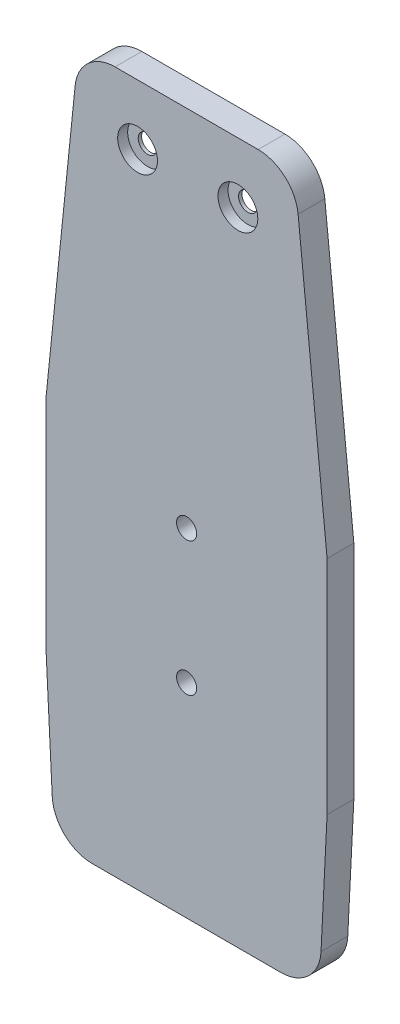
SolidWorks part; units mm, degrees
ref_plane "Front Plane" through (0, 0, 0) normal (0, 0, 1) x (1, 0, 0)
ref_plane "Top Plane" through (0, 0, 0) normal (0, 1, 0) x (1, 0, 0)
ref_plane "Right Plane" through (0, 0, 0) normal (1, 0, 0) x (0, 0, -1)
sketch "Sketch1" plane through (0, 0, 0) normal (0, 0, 1) x (1, 0, 0)
  line L8 (37.09, -18.2996) -> (38, -0.0999)
  line L9 (38, -0.0999) -> (38, 33.052)
  line L10 (33.663, 75.4585) -> (38, 33.052)
  line L11 (6.3059, 80.848) -> (27.6941, 80.848)
  line L12 (0.337, 75.4585) -> (-4, 33.052)
  line L13 (-4, -0.0999) -> (-4, 33.052)
  line L14 (-4, -0.0999) -> (-3.09, -18.2996)
  line L15 (2.9025, -24) -> (31.0975, -24)
  arc A4 (33.663, 75.4585) -> (27.6941, 80.848) centre (27.6941, 74.848) ccw
  arc A5 (0.337, 75.4585) -> (6.3059, 80.848) centre (6.3059, 74.848) cw
  arc A6 (-3.09, -18.2996) -> (2.9025, -24) centre (2.9025, -18) ccw
  arc A7 (31.0975, -24) -> (37.09, -18.2996) centre (31.0975, -18) ccw
extrude "Boss-Extrude4" add sketch "Sketch1" along normal blind 2
sketch "Sketch5" plane through (0, 0, 0) normal (0, 0, -1) x (-1, 0, 0)
  line L8 (-33.663, 75.4585) -> (-38, 33.052)
  line L9 (-38, 33.052) -> (-38, -0.0999)
  line L10 (-38, -0.0999) -> (-37.09, -18.2996)
  line L11 (-31.0975, -24) -> (-2.9025, -24)
  line L12 (3.09, -18.2996) -> (4, -0.0999)
  line L13 (4, -0.0999) -> (4, 33.052)
  line L14 (4, 33.052) -> (-0.337, 75.4585)
  line L15 (-6.3059, 80.848) -> (-27.6941, 80.848)
  line L16 (-31.0975, -22) -> (-2.9025, -22)
  line L17 (1.0925, -18.1998) -> (2, -0.05)
  line L18 (2, -0.05) -> (2, 32.95)
  line L19 (2, 32.95) -> (-2.3266, 75.255)
  line L20 (-6.3059, 78.848) -> (-27.6941, 78.848)
  line L21 (-31.6734, 75.255) -> (-36, 32.95)
  line L22 (-36, 32.95) -> (-36, -0.05)
  line L23 (-36, -0.05) -> (-35.0925, -18.1998)
  line L24 (-31.0975, -22) -> (-2.9025, -22)
  line L25 (1.0925, -18.1998) -> (2, -0.05)
  line L26 (2, -0.05) -> (2, 32.95)
  line L27 (2, 32.95) -> (-2.3266, 75.255)
  line L28 (-6.3059, 78.848) -> (-27.6941, 78.848)
  line L29 (-31.6734, 75.255) -> (-36, 32.95)
  line L30 (-36, 32.95) -> (-36, -0.05)
  line L31 (-36, -0.05) -> (-35.0925, -18.1998)
  arc A4 (-27.6941, 80.848) -> (-33.663, 75.4585) centre (-27.6941, 74.848) ccw
  arc A5 (-37.09, -18.2996) -> (-31.0975, -24) centre (-31.0975, -18) ccw
  arc A6 (-2.9025, -24) -> (3.09, -18.2996) centre (-2.9025, -18) ccw
  arc A7 (-0.337, 75.4585) -> (-6.3059, 80.848) centre (-6.3059, 74.848) ccw
  arc A8 (-35.0925, -18.1998) -> (-31.0975, -22) centre (-31.0975, -18) ccw
  arc A9 (-2.9025, -22) -> (1.0925, -18.1998) centre (-2.9025, -18) ccw
  arc A10 (-2.3266, 75.255) -> (-6.3059, 78.848) centre (-6.3059, 74.848) ccw
  arc A11 (-27.6941, 78.848) -> (-31.6734, 75.255) centre (-27.6941, 74.848) ccw
  arc A12 (-35.0925, -18.1998) -> (-31.0975, -22) centre (-31.0975, -18) ccw
  arc A13 (-2.9025, -22) -> (1.0925, -18.1998) centre (-2.9025, -18) ccw
  arc A14 (-2.3266, 75.255) -> (-6.3059, 78.848) centre (-6.3059, 74.848) ccw
  arc A15 (-27.6941, 78.848) -> (-31.6734, 75.255) centre (-27.6941, 74.848) ccw
  dimension "D1" = 2
  dimension "D2" = 2
extrude "Boss-Extrude5" add sketch "Sketch5" along normal blind 2
sketch "Sketch6" plane through (0, 0, 0) normal (0, 0, -1) x (-1, 0, 0)
  line L0 (-30.625, 65.848) -> (-3.375, 65.848)
  line L16 (-31.0975, -20) -> (-2.9025, -20)
  line L17 (-0.905, -18.0999) -> (0, 0)
  line L18 (-34, 0) -> (-33.095, -18.0999)
  line L19 (-34, 32.848) -> (-34, 0)
  line L20 (-29.6837, 75.0515) -> (-34, 32.848)
  line L21 (-6.3059, 76.848) -> (-27.6941, 76.848)
  line L22 (0, 32.848) -> (-4.3163, 75.0515)
  line L23 (0, 0) -> (0, 32.848)
  line L24 (-31.0975, -20) -> (-2.9025, -20)
  line L25 (-0.905, -18.0999) -> (0, 0)
  line L26 (-34, 0) -> (-33.095, -18.0999)
  line L27 (-34, 32.848) -> (-34, 0)
  line L28 (-30.625, 65.848) -> (-34, 32.848)
  line L30 (0, 32.848) -> (-3.375, 65.848)
  line L31 (0, 0) -> (0, 32.848)
  arc A8 (-33.095, -18.0999) -> (-31.0975, -20) centre (-31.0975, -18) ccw
  arc A9 (-2.9025, -20) -> (-0.905, -18.0999) centre (-2.9025, -18) ccw
  arc A10 (-27.6941, 76.848) -> (-29.6837, 75.0515) centre (-27.6941, 74.848) ccw
  arc A11 (-4.3163, 75.0515) -> (-6.3059, 76.848) centre (-6.3059, 74.848) ccw
  arc A12 (-33.095, -18.0999) -> (-31.0975, -20) centre (-31.0975, -18) ccw
  arc A13 (-2.9025, -20) -> (-0.905, -18.0999) centre (-2.9025, -18) ccw
  dimension "D1" = 2
extrude "Boss-Extrude6" add sketch "Sketch6" along normal blind 2
fillet "Fillet1" radius 2 2 edges at (3.375, 65.848, -1) (30.625, 65.848, -1)
hole_wizard "CBORE for #3 Binding Head Machine Screw1" positions "Sketch8" profile "Sketch7" counterbore size "#3" standard "ANSI Inch" end condition through all
sketch "Sketch8" plane through (0, 0, 2) normal (0, 0, 1) x (1, 0, 0)
  line L0 (27.6941, 80.848) -> (6.3059, 80.848) construction
  point P0 (24.6638, 71.848)
  point P2 (9.6645, 71.848)
  dimension "D1" = 9
  dimension "D2" = 9
sketch "Sketch7" plane through (24.6638, 71.848, 2) normal (1, 0, 0) x (0, -1, 0)
  line L0 (0, 0) -> (0, 4)
  line L1 (0, 4) -> (1.397, 4)
  line L3 (1.397, 4) -> (1.397, 1.4986)
  line L4 (1.397, 1.4986) -> (2.9769, 1.4986)
  line L5 (2.9769, 1.4986) -> (2.9769, 0)
  line L7 (2.9769, 0) -> (0, 0)
  line L11 (0, -6.35) -> (0, 107.95) construction
  dimension "Thru Hole Dia." = 2.794
  dimension "Thru Hole Depth" = 4
  dimension "C'Bore Dia." = 5.9538
  dimension "C'Bore Depth" = 1.4986
sketch "Sketch9" plane through (0, 0, 2) normal (0, 0, 1) x (1, 0, 0)
  circle A0 centre (17, 6.4761) radius 1.5
  circle A1 centre (17, 26.4761) radius 1.5
  dimension "D3" = 3
  dimension "D4" = 3
sketch "Sketch10" plane through (0, 0, 2) normal (0, 0, 1) x (1, 0, 0)
  circle A0 centre (17, 6.4761) radius 1.5 construction
  circle A1 centre (17, 6.4761) radius 1.5
extrude "Cut-Extrude1" cut sketch "Sketch10" against normal blind 5
extrude "Cut-Extrude2" cut sketch "Sketch9" against normal blind 5
